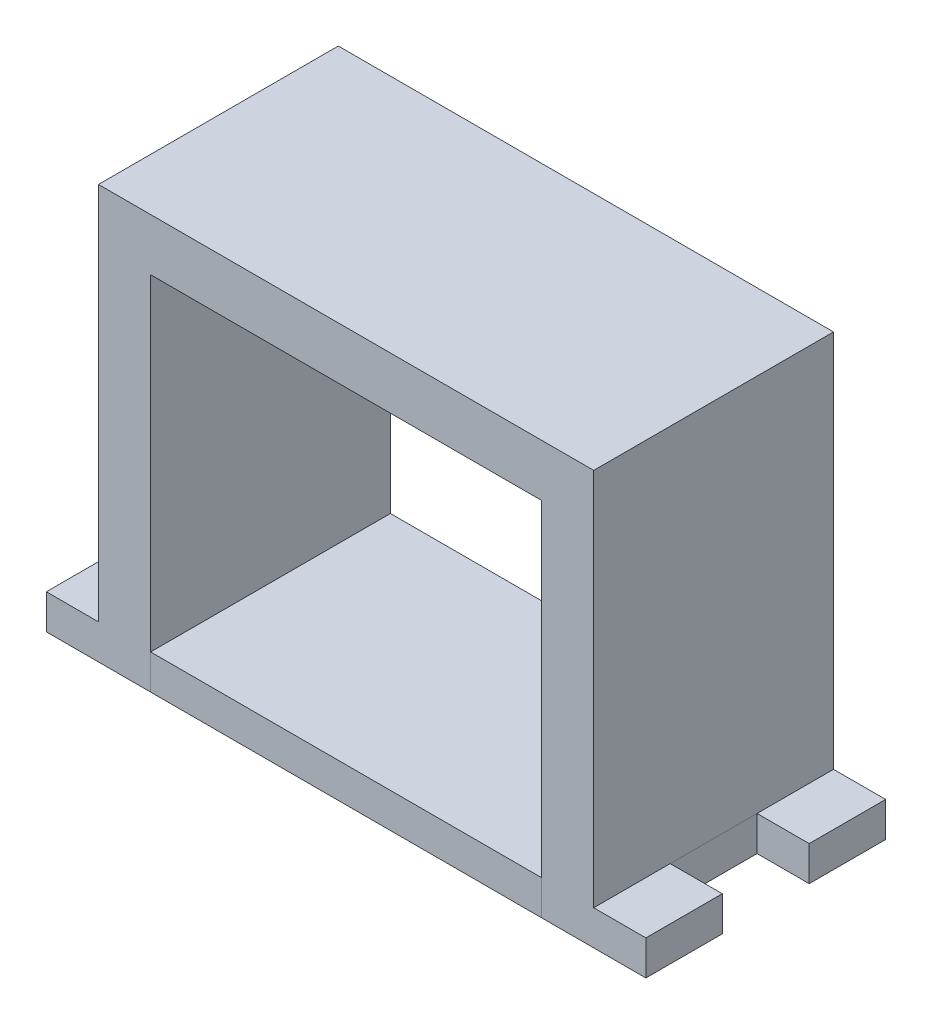
SolidWorks part; units mm, degrees
ref_plane "Front Plane" through (0, 0, 0) normal (0, 0, 1) x (1, 0, 0)
ref_plane "Top Plane" through (0, 0, 0) normal (0, 1, 0) x (1, 0, 0)
ref_plane "Right Plane" through (0, 0, 0) normal (1, 0, 0) x (0, 0, -1)
sketch "Sketch1" plane through (0, 0, 0) normal (0, 1, 0) x (1, 0, 0)
  line L0 (0, -1.9) -> (0, -6.9) construction
  line L1 (-14.25, -6.9) -> (14.25, -6.9)
  line L2 (-14.25, -6.9) -> (-14.25, 6.9)
  line L3 (-14.25, 6.9) -> (14.25, 6.9)
  line L4 (14.25, -6.9) -> (14.25, 6.9)
  line L5 (-14.25, -6.9) -> (14.25, 6.9) construction
  line L6 (-14.25, 6.9) -> (14.25, -6.9) construction
  line L7 (11.25, 6.9) -> (11.25, -6.9)
  line L8 (-14.25, 6.9) -> (-11.25, 6.9)
  line L9 (-14.25, 6.9) -> (-14.25, -6.9)
  line L10 (-14.25, -6.9) -> (-11.25, -6.9)
  line L11 (-11.25, 6.9) -> (-11.25, -6.9)
  circle A0 centre (0, 0) radius 1.9
  point P0 (0, 0)
  point P13 (-11.25, -6.9)
  dimension "D1" = 3.8
  dimension "D2" = 5
  dimension "D3" = 28.5
  dimension "D4" = 3
extrude "Boss-Extrude1" add sketch "Sketch1" along normal blind 3 contours L3 L11 L1 L7 A0 | A0 | L11 L3 L2 L1 | L3 L7 L1 L4 region at (-12.75, 0, 0) region at (-10.9861, 0, 0) region at (12.75, 0, 0) region at (0, 0, 0)
extrude "Cut-Extrude1" cut sketch "Sketch1<4>" along normal blind 2 contours A0 region at (0, 0, 0)
sketch "Sketch1<4>" plane through (0, 0, 0) normal (0, 1, 0) x (1, 0, 0) same geometry as "Sketch1"
extrude "Boss-Extrude2" add sketch "Sketch1<6>" against normal blind 18.8 contours L11 L3 L2 L1 | L3 L7 L1 L4 region at (-12.75, 0, 0) region at (12.75, 0, 0)
sketch "Sketch1<6>" plane through (0, 0, 0) normal (0, 1, 0) x (1, 0, 0) same geometry as "Sketch1"
sketch "Sketch3" plane through (0, -18.8, 0) normal (0, -1, 0) x (1, 0, 0)
  line L0 (-12.75, 6.9) -> (-12.75, -6.9) construction
  line L1 (-14.25, 6.9) -> (-11.25, 6.9) construction
  line L2 (-14.25, -6.9) -> (-11.25, -6.9) construction
  line L3 (-11.25, -6.9) -> (-11.25, 6.9) construction
  line L4 (-14.25, -2.5) -> (-11.25, -2.5)
  line L5 (-14.25, -2.5) -> (-14.25, 2.5)
  line L6 (-14.25, 2.5) -> (-11.25, 2.5)
  line L7 (-11.25, -2.5) -> (-11.25, 2.5)
  line L8 (-14.25, -2.5) -> (-11.25, 2.5) construction
  line L9 (-14.25, 2.5) -> (-11.25, -2.5) construction
  line L10 (0, 6.9) -> (0, -6.9) construction
  line L11 (-11.25, 6.9) -> (11.25, 6.9) construction
  line L12 (-11.25, -6.9) -> (11.25, -6.9) construction
  line L13 (11.25, -2.5) -> (11.25, 2.5)
  line L14 (14.25, -2.5) -> (11.25, -2.5)
  line L15 (14.25, -2.5) -> (14.25, 2.5)
  line L16 (14.25, 2.5) -> (11.25, 2.5)
  line L17 (-14.25, 2.5) -> (-14.25, 6.9)
  line L18 (-14.25, 6.9) -> (14.25, 6.9)
  line L19 (14.25, 6.9) -> (14.25, -6.9) construction
  line L20 (14.25, 6.9) -> (14.25, 2.5)
  line L21 (14.25, -2.5) -> (14.25, -6.9)
  line L22 (11.25, -6.9) -> (14.25, -6.9) construction
  line L23 (14.25, -6.9) -> (-14.25, -6.9)
  line L24 (-14.25, -6.9) -> (-14.25, -2.5)
  line L25 (-11.25, -2.5) -> (-11.25, -6.9)
  line L26 (-11.25, 2.5) -> (-11.25, 6.9)
  line L27 (11.25, 6.9) -> (11.25, 2.5)
  line L28 (11.25, -2.5) -> (11.25, -6.9)
  line L29 (14.25, -6.9) -> (17.25, -6.9)
  line L30 (-14.25, 6.9) -> (-17.25, 6.9)
  line L31 (-14.25, 6.9) -> (-14.25, -6.9)
  line L32 (-14.25, -6.9) -> (-17.25, -6.9)
  line L33 (-17.25, 6.9) -> (-17.25, -6.9)
  line L34 (17.25, 6.9) -> (17.25, -6.9)
  line L35 (14.25, 6.9) -> (17.25, 6.9)
  line L36 (-14.25, 2.5) -> (-17.25, 2.5)
  line L37 (-14.25, -2.5) -> (-17.25, -2.5)
  line L38 (14.25, 2.5) -> (17.25, 2.5)
  line L39 (14.25, -2.5) -> (17.25, -2.5)
  point P6 (-12.75, 0)
  line M10 (-11.25, -6.9) -> (-11.25, 6.9)
  line M11 (-11.25, 6.9) -> (-14.25, 6.9)
  line M12 (-14.25, 6.9) -> (-14.25, -6.9)
  line M13 (-14.25, -6.9) -> (-11.25, -6.9)
  dimension "D1" = 5
  dimension "D2" = 3
extrude "Boss-Extrude6" add sketch "Sketch3" along normal blind 2 contours L6 M12 M10 M11 | L4 M12 M13 M10 | L18 L27 L16 L20 | L14 L28 L23 L21 region at (-12.75, -18.8, -4.7) region at (-12.75, -18.8, 4.7) region at (12.75, -18.8, -4.7) region at (12.75, -18.8, 4.7)
extrude "Boss-Extrude12" add sketch "Sketch3<7>" along normal blind 2 contours L36 L30 L33 M12 | L37 L33 L32 M12 | L20 L38 L34 L35 | L39 L21 L29 L34 region at (-15.75, -18.8, -4.7) region at (-15.75, -18.8, 4.7) region at (15.75, -18.8, -4.7) region at (15.75, -18.8, 4.7)
sketch "Sketch3<7>" plane through (0, -18.8, 0) normal (0, -1, 0) x (1, 0, 0) same geometry as "Sketch3"
extrude "Boss-Extrude13" add sketch "Sketch3<8>" along normal blind 2 separate body contours L6 L4 M12 M10 | L28 L13 L27 L18 L23 M10 | L15 L16 L13 L14 region at (-12.75, -18.8, 0) region at (0, -18.8, 0) region at (12.75, -18.8, 0)
sketch "Sketch3<8>" plane through (0, -18.8, 0) normal (0, -1, 0) x (1, 0, 0) same geometry as "Sketch3"
